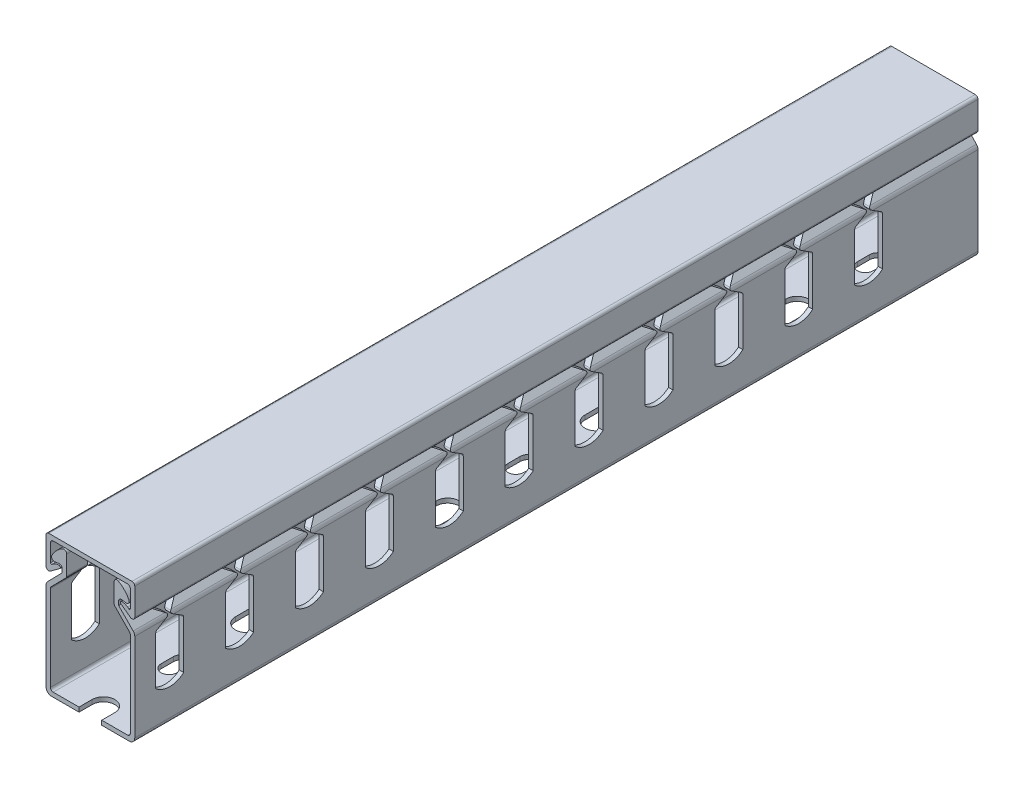
SolidWorks part; units mm, degrees
ref_plane "Front Plane" through (0, 0, 0) normal (0, 0, 1) x (1, 0, 0)
ref_plane "Top Plane" through (0, 0, 0) normal (0, 1, 0) x (1, 0, 0)
ref_plane "Right Plane" through (0, 0, 0) normal (1, 0, 0) x (0, 0, -1)
sketch "Sketch1" plane through (0, 0, 0) normal (0, 0, 1) x (1, 0, 0)
  line L0 (-12.7, 10.6985) -> (12.7, 10.6985) construction
  line L1 (12.7, -20) -> (-12.7, -20) construction
  line L2 (12.7, -20) -> (12.7, 20) construction
  line L3 (12.7, 20) -> (-12.7, 20) construction
  line L4 (-12.7, -20) -> (-12.7, 20) construction
  line L5 (0, 20) -> (0, -20) construction
  line L6 (12.7, 0) -> (-12.7, 0) construction
  line L7 (-12.7, 13.7872) -> (12.7, 13.7872) construction
  line L8 (6.8085, 20) -> (6.8085, 10.6985) construction
  line L9 (-6.8085, 20) -> (6.8085, 10.6985) construction
  line L10 (-6.8085, 20) -> (-6.8085, 10.6985) construction
  line L11 (-12.7, 18.222) -> (12.7, 18.222) construction
  line L12 (-12.7, 13.6284) -> (12.7, 13.6284) construction
  line L13 (-11.4341, 10.8542) -> (-7.685, 13.6284) construction
  line L14 (-10.1877, 13.798) -> (-6.8085, 14.3635) construction
  line L15 (12.7, 7.4) -> (6.8085, 13.4162) construction
  circle A0 centre (-11.9062, 11.4923) radius 0.7938 construction
  circle A1 centre (-10.3187, 14.5809) radius 0.7937 construction
  circle A2 centre (-7.6022, 17.4283) radius 0.7938 construction
  arc A3 (-7.9835, 18.1244) -> (-11.0321, 14.929) centre (-4.4831, 11.7329) ccw construction
  point P0 (0, 0)
  point P4 (11.43, 0)
  point P13 (0, 15.3493)
  point P16 (-11.1125, 13.7872)
  point P21 (-11.1125, 11.4923)
  point P26 (-10.3188, 13.7872)
  point P27 (-10.3188, 13.7872)
  point P28 (-11.1125, 14.5809)
  point P36 (12.7, 7.4)
  dimension "D6" = 7.2873
  dimension "Width" = 25.4
  dimension "Heigth" = 40
  dimension "Wall Thickness" = 1.27
  dimension "Cap Height" = 9.3015
  dimension "Lip Height" = 6.2128
  dimension "D1" = 13.6169
  dimension "D2" = 1.778
  dimension "Lip From Edge" = 1.5875
  dimension "D4" = 0.1588
  dimension "D5" = 36.5
  dimension "D3" = 80.5
  dimension "Shoulder Height" = 27.4
  dimension "D7" = 44.4
sketch "Sketch3" plane through (0, 0, 0) normal (1, 0, 0) x (0, 0, -1)
  line L0 (120.65, 0) -> (-120.65, 0) construction
  line L1 (-120.65, 20) -> (-120.65, -20) construction
  line L2 (-120.65, -20) -> (120.65, -20) construction
  line L3 (120.65, -20) -> (120.65, 20) construction
  line L4 (120.65, 20) -> (-120.65, 20) construction
  line L5 (-106.65, 20) -> (-106.65, 9.8437) construction
  line L6 (-106.65, 9.8437) -> (-110.523, 7.4) construction
  line L7 (-110.523, 7.4) -> (-110.777, 7.4) construction
  line L8 (-110.777, 7.4) -> (-114.65, 9.8437) construction
  line L9 (-114.65, 9.8437) -> (-114.65, 20) construction
  line L10 (-110.777, 7.4) -> (-114.65, 4.9563) construction
  line L11 (-114.65, 4.9563) -> (-114.65, -9.1796) construction
  line L12 (-114.65, -9.1796) -> (-106.65, -9.1796) construction
  line L13 (-106.65, -9.1796) -> (-106.65, 4.9563) construction
  line L14 (-110.523, 7.4) -> (-106.65, 4.9563) construction
  line L15 (-110.65, 7.4) -> (-110.65, -9.1796) construction
  line L16 (-110.65, 7.4) -> (-110.65, 20) construction
  line L17 (-114.65, 4.9563) -> (-106.65, 4.9563) construction
  line L18 (0, 7.4) -> (-110.523, 7.4) construction
  line L19 (-114.65, 9.8437) -> (-114.65, 4.9563) construction
  line L20 (-110.777, 7.4) -> (-114.65, 7.4) construction
  line L21 (-106.65, 4.9563) -> (-94.65, 4.9563) construction
  line L22 (-94.65, 4.9563) -> (-86.65, 4.9563) construction
  line L23 (-90.65, 4.9563) -> (-90.65, -9.1796) construction
  line L24 (6.35, 20) -> (6.35, -20) construction
  line L25 (-6.35, 20) -> (-6.35, -20) construction
  arc A0 (-114.65, -9.1796) -> (-106.65, -9.1796) centre (-110.65, -4.7075) ccw construction
  circle A1 centre (-111.5207, 7.4) radius 0.3969 construction
  circle A2 centre (-109.7793, 7.4) radius 0.3969 construction
  point P29 (-86.65, 4.9563)
  point P30 (-94.65, 4.9563)
  point P31 (-94.65, 4.9563)
  point P32 (-90.65, 4.9563)
  point P34 (6.35, 0)
  point P39 (-6.35, 0)
  dimension "D2" = 6
  dimension "D6" = 0.7937
  dimension "Length" = 241.3
  dimension "Side Cut Out Width" = 8
  dimension "D3" = 6
  dimension "D1" = 10.8204
  dimension "D4" = 64.5
  dimension "D5" = 0.254
  dimension "Cut Spacing" = 12
  dimension "Cut Center To Center" = 20
  dimension "D7" = 127
  dimension "D8" = 127
sketch "Sketch4" plane through (0, 0, 0) normal (0, 1, 0) x (1, 0, 0)
  line L0 (0, -124.4) -> (0, -116.9) construction
  line L1 (-12.7, 120.65) -> (12.7, 120.65) construction
  line L2 (-12.7, 120.65) -> (-12.7, -120.65) construction
  line L3 (-12.7, -120.65) -> (12.7, -120.65) construction
  line L4 (12.7, 120.65) -> (12.7, -120.65) construction
  line L5 (0, -120.65) -> (0, 120.65) construction
  line L6 (-12.7, 0) -> (12.7, 0) construction
  line L7 (-3.25, -124.4) -> (-3.25, -116.9) construction
  line L8 (3.25, -124.4) -> (3.25, -116.9) construction
  line L9 (0, -98.15) -> (0, -94.65) construction
  line L10 (-2.25, -98.15) -> (-2.25, -94.65) construction
  line L11 (2.25, -98.15) -> (2.25, -94.65) construction
  line L12 (0, -75.9) -> (0, -68.4) construction
  line L13 (-3.25, -75.9) -> (-3.25, -68.4) construction
  line L14 (3.25, -75.9) -> (3.25, -68.4) construction
  line L15 (0, -45.4) -> (0, -48.9) construction
  line L16 (2.25, -45.4) -> (2.25, -48.9) construction
  line L17 (-2.25, -45.4) -> (-2.25, -48.9) construction
  line L18 (-12.7, 6.35) -> (12.7, 6.35) construction
  line L19 (-12.7, -6.35) -> (12.7, -6.35) construction
  arc A0 (-3.25, -124.4) -> (3.25, -124.4) centre (0, -124.4) ccw construction
  arc A1 (3.25, -116.9) -> (-3.25, -116.9) centre (0, -116.9) ccw construction
  arc A2 (-2.25, -98.15) -> (2.25, -98.15) centre (0, -98.15) ccw construction
  arc A3 (2.25, -94.65) -> (-2.25, -94.65) centre (0, -94.65) ccw construction
  arc A4 (-3.25, -75.9) -> (3.25, -75.9) centre (0, -75.9) ccw construction
  arc A5 (3.25, -68.4) -> (-3.25, -68.4) centre (0, -68.4) ccw construction
  arc A6 (2.25, -45.4) -> (-2.25, -45.4) centre (0, -45.4) ccw construction
  arc A7 (-2.25, -48.9) -> (2.25, -48.9) centre (0, -48.9) ccw construction
  point P0 (0, 0)
  point P5 (0, -120.65)
  point P13 (0, -96.4)
  point P18 (0, -92.4)
  point P19 (0, -100.4)
  point P20 (0, -113.65)
  point P21 (0, -127.65)
  point P24 (0, -72.15)
  point P31 (0, -47.15)
  point P40 (0, -79.15)
  point P41 (0, -65.15)
  dimension "Large Hole Radius" = 3.25
  dimension "Large Hole Length" = 14
  dimension "Slot With" = 8
  dimension "End Hole Spacing" = 48.5
  dimension "D4" = 24.25
  dimension "Hole Spacing" = 25
  dimension "Mounting Hole Diameter" = 4.5
sketch "Sketch5" plane through (0, 0, 0) normal (0, 0, 1) x (1, 0, 0)
  line L0 (-6.8085, 17.4283) -> (-6.8085, 11.6011)
  line L1 (-6.8085, 20) -> (-6.8085, 10.6985) construction
  line L2 (-6.8085, 11.6011) -> (-11.43, 6.8817)
  line L3 (-11.43, 6.8817) -> (-11.43, -18.73)
  line L4 (-11.43, -18.73) -> (11.43, -18.73)
  line L5 (11.43, -18.73) -> (11.43, 6.8817)
  line L6 (11.43, 6.8817) -> (6.8085, 11.6011)
  line L7 (6.8085, 11.6011) -> (6.8085, 17.4283)
  line L8 (6.8085, 20) -> (6.8085, 10.6985) construction
  line L9 (12.7, 7.4) -> (6.8085, 13.4162) construction
  line L10 (0, 20) -> (0, -20) construction
  line L11 (11.43, 0) -> (12.7, 0) construction
  line L12 (8.0785, 12.1194) -> (6.8085, 12.1194) construction
  line L13 (-10.1877, 13.798) -> (-6.8085, 14.3635) construction
  line L14 (-10.1877, 13.798) -> (-8.0785, 14.151)
  line L15 (-8.0785, 14.151) -> (-8.0785, 12.1194)
  line L16 (-8.0785, 12.1194) -> (-12.7, 7.4)
  line L17 (-12.7, -20) -> (-12.7, 20) construction
  line L18 (-12.7, 7.4) -> (-12.7, -20)
  line L19 (-12.7, -20) -> (12.7, -20)
  line L20 (12.7, -20) -> (12.7, 7.4)
  line L21 (12.7, 7.4) -> (8.0785, 12.1194)
  line L22 (8.0785, 12.1194) -> (8.0785, 14.151)
  line L23 (6.8085, 12.1194) -> (-6.8085, 12.1194) construction
  line L24 (-6.8085, 12.1194) -> (-8.0785, 12.1194) construction
  line L25 (11.43, 6.8817) -> (12.3374, 7.7703) construction
  line L26 (-12.7, 18.222) -> (12.7, 18.222) construction
  line L27 (10.1877, 13.798) -> (8.0785, 14.151)
  line L28 (11.43, -18.73) -> (11.43, -20) construction
  line L29 (-12.7, 20) -> (-12.7, 11.4923)
  line L30 (-12.7, 20) -> (12.7, 20)
  line L31 (-11.4341, 10.8542) -> (-8.7512, 12.8395)
  line L32 (-11.4341, 10.8542) -> (-7.685, 13.6284) construction
  line L33 (12.7, 20) -> (12.7, 11.4923)
  line L34 (12.7, -20) -> (12.7, 20) construction
  line L35 (8.7512, 12.8395) -> (11.4341, 10.8542)
  line L36 (-12.7, 10.6985) -> (12.7, 10.6985) construction
  line L37 (-11.43, 12.4371) -> (-11.43, 18.73)
  line L38 (-11.43, 18.73) -> (11.43, 18.73)
  line L39 (11.43, 18.73) -> (11.43, 12.4371)
  line L40 (-11.43, 18.73) -> (-11.43, 20) construction
  line L41 (-11.43, 18.73) -> (-12.7, 18.73) construction
  line L42 (-11.43, 12.4371) -> (-10.6707, 12.999)
  line L43 (-11.0503, 12.7181) -> (-10.2949, 11.6972) construction
  line L44 (-8.9869, 13.5542) -> (-8.9869, 13.158) construction
  line L45 (10.6707, 12.999) -> (11.43, 12.4371)
  line L46 (10.6707, 12.999) -> (9.9153, 11.9781) construction
  circle A0 centre (-7.6022, 17.4283) radius 0.7938 construction
  arc A1 (-7.9835, 18.1244) -> (-11.0321, 14.929) centre (-4.4831, 11.7329) ccw construction
  arc A2 (-7.9835, 18.1244) -> (-11.0321, 14.929) centre (-4.4831, 11.7329) ccw
  circle A3 centre (-10.3187, 14.5809) radius 0.7937 construction
  arc A4 (-11.0321, 14.929) -> (-10.1877, 13.798) centre (-10.3187, 14.5809) ccw
  arc A5 (-6.8085, 17.4283) -> (-7.9835, 18.1244) centre (-7.6022, 17.4283) ccw
  arc A6 (7.9835, 18.1244) -> (6.8085, 17.4283) centre (7.6022, 17.4282) ccw
  arc A7 (10.1877, 13.798) -> (11.0321, 14.929) centre (10.3187, 14.5809) ccw
  arc A8 (7.9835, 18.1244) -> (11.0321, 14.929) centre (4.4831, 11.7329) cw
  circle A9 centre (-11.9062, 11.4923) radius 0.7938 construction
  arc A10 (-12.7, 11.4923) -> (-11.4341, 10.8542) centre (-11.9062, 11.4923) ccw
  arc A11 (11.4341, 10.8542) -> (12.7, 11.4923) centre (11.9062, 11.4923) ccw
  arc A12 (-8.7512, 12.8395) -> (-8.9869, 13.5542) centre (-8.9869, 13.158) ccw
  arc A13 (-10.6707, 12.999) -> (-8.9869, 13.5542) centre (-8.9869, 10.7234) cw
  arc A14 (8.7512, 12.8395) -> (8.9869, 13.5542) centre (8.9869, 13.158) cw
  arc A15 (8.9869, 13.5542) -> (10.6707, 12.999) centre (8.9869, 10.7234) cw
  point P10 (0, -18.73)
  point P81 (0, 18.73)
  dimension "D2" = 0.3962
  dimension "D1" = 3.3376
extrude "Boss-Extrude1" add sketch "Sketch5" along normal up to vertex (120.65 mm away) and the other way up to vertex (120.65 mm away) up to point (0, -20, 120.65) other way up to point (0, -20, -120.65)
fillet "Fillet1" radius 0.254 2 edges at (-11.43, 12.4371, 0) (11.43, 12.4371, 0)
fillet "Fillet2" radius 0.7937 4 edges at (12.7, 20, 0) (11.43, 18.73, 0) (-11.43, 18.73, 0) (-12.7, 20, 0)
fillet "Fillet3" radius 1.5875 4 edges at (-12.7, -20, 0) (12.7, -20, 0) (12.7, 7.4, 0) (-12.7, 7.4, 0)
fillet "Fillet4" radius 0.7937 8 edges at (-11.43, -18.73, 0) (11.43, -18.73, 0) (8.0785, 14.151, 0) (-8.0785, 14.151, 0) (-11.43, 6.8817, 0) (-6.8085, 11.6011, 0) (6.8085, 11.6011, 0) (11.43, 6.8817, 0)
sketch "Sketch6" plane through (0, 0, 0) normal (1, 0, 0) x (0, 0, -1)
  line L0 (-114.65, 20) -> (-114.65, 10.2814)
  line L1 (-114.65, 4.9563) -> (-114.65, -9.1796) construction
  line L2 (-110.777, 7.4) -> (-114.65, 4.9563) construction
  line L3 (-106.65, -9.1796) -> (-106.65, 4.9563) construction
  line L4 (-110.523, 7.4) -> (-106.65, 4.9563) construction
  line L5 (-106.65, 9.8437) -> (-110.523, 7.4) construction
  line L6 (-106.65, 20) -> (-106.65, 9.8437) construction
  line L7 (-110.777, 7.4) -> (-114.65, 9.8437) construction
  line L8 (-114.65, 4.5186) -> (-114.65, -9.1796)
  line L9 (-111.309, 7.0644) -> (-114.2798, 5.1899)
  line L10 (-106.65, -9.1796) -> (-106.65, 4.5186)
  line L11 (-109.991, 7.0644) -> (-107.0202, 5.1899)
  line L12 (-107.0202, 9.6101) -> (-109.991, 7.7356)
  line L13 (-106.65, 20) -> (-106.65, 10.2814)
  line L14 (-111.309, 7.7356) -> (-114.2798, 9.6101)
  line L15 (-106.65, 20) -> (-114.65, 20)
  circle A0 centre (-109.7793, 7.4) radius 0.3969 construction
  circle A1 centre (-111.5207, 7.4) radius 0.3969 construction
  arc A2 (-109.991, 7.7356) -> (-109.991, 7.0644) centre (-109.7793, 7.4) ccw
  arc A3 (-111.309, 7.0644) -> (-111.309, 7.7356) centre (-111.5207, 7.4) ccw
  arc A4 (-114.65, -9.1796) -> (-106.65, -9.1796) centre (-110.65, -4.7075) ccw construction
  arc A5 (-114.65, -9.1796) -> (-106.65, -9.1796) centre (-110.65, -4.7075) ccw
  arc A6 (-107.0202, 9.6101) -> (-106.65, 10.2814) centre (-107.4437, 10.2814) ccw
  arc A7 (-106.65, 4.5186) -> (-107.0202, 5.1899) centre (-107.4437, 4.5186) ccw
  arc A8 (-114.65, 4.5186) -> (-114.2798, 5.1899) centre (-113.8562, 4.5186) cw
  arc A9 (-114.65, 10.2814) -> (-114.2798, 9.6101) centre (-113.8562, 10.2814) ccw
  dimension "D1" = 0.7937
extrude "Cut-Extrude2" cut sketch "Sketch6" against normal through all both and the other way through all
pattern_linear "LPattern2" count 11 spacing 20 along (0, 0, -1) of "Cut-Extrude2"
sketch "Sketch7" plane through (0, -20, 0) normal (0, -1, 0) x (1, 0, 0)
  line L0 (-3.25, 124.4) -> (-3.25, 116.9) construction
  line L1 (3.25, 124.4) -> (3.25, 116.9) construction
  line L2 (-3.25, 124.4) -> (-3.25, 116.9)
  line L3 (3.25, 124.4) -> (3.25, 116.9)
  line L4 (-2.25, 98.15) -> (-2.25, 94.65) construction
  line L5 (2.25, 98.15) -> (2.25, 94.65) construction
  line L6 (-2.25, 98.15) -> (-2.25, 94.65)
  line L7 (2.25, 98.15) -> (2.25, 94.65)
  arc A0 (3.25, 124.4) -> (-3.25, 124.4) centre (0, 124.4) ccw construction
  arc A1 (-3.25, 116.9) -> (3.25, 116.9) centre (0, 116.9) ccw construction
  arc A2 (3.25, 124.4) -> (-3.25, 124.4) centre (0, 124.4) ccw
  arc A3 (-3.25, 116.9) -> (3.25, 116.9) centre (0, 116.9) ccw
  arc A4 (2.25, 98.15) -> (-2.25, 98.15) centre (0, 98.15) ccw construction
  arc A5 (-2.25, 94.65) -> (2.25, 94.65) centre (0, 94.65) ccw construction
  arc A6 (2.25, 98.15) -> (-2.25, 98.15) centre (0, 98.15) ccw
  arc A7 (-2.25, 94.65) -> (2.25, 94.65) centre (0, 94.65) ccw
extrude "Cut-Extrude3" cut sketch "Sketch7" against normal up to vertex (1.27 mm away) up to point (10.6363, -18.73, 120.65)
sketch "Sketch8" plane through (0, -20, 0) normal (0, -1, 0) x (1, 0, 0)
  line L0 (-2.25, 45.4) -> (-2.25, 48.9) construction
  line L1 (2.25, 45.4) -> (2.25, 48.9) construction
  line L2 (3.25, 75.9) -> (3.25, 68.4) construction
  line L3 (-3.25, 75.9) -> (-3.25, 68.4) construction
  line L4 (-2.25, 45.4) -> (-2.25, 48.9)
  line L5 (2.25, 45.4) -> (2.25, 48.9)
  line L6 (3.25, 75.9) -> (3.25, 68.4)
  line L7 (-3.25, 75.9) -> (-3.25, 68.4)
  arc A0 (-2.25, 45.4) -> (2.25, 45.4) centre (0, 45.4) ccw construction
  arc A1 (2.25, 48.9) -> (-2.25, 48.9) centre (0, 48.9) ccw construction
  arc A2 (3.25, 75.9) -> (-3.25, 75.9) centre (0, 75.9) ccw construction
  arc A3 (-3.25, 68.4) -> (3.25, 68.4) centre (0, 68.4) ccw construction
  arc A4 (-2.25, 45.4) -> (2.25, 45.4) centre (0, 45.4) ccw
  arc A5 (2.25, 48.9) -> (-2.25, 48.9) centre (0, 48.9) ccw
  arc A6 (3.25, 75.9) -> (-3.25, 75.9) centre (0, 75.9) ccw
  arc A7 (-3.25, 68.4) -> (3.25, 68.4) centre (0, 68.4) ccw
extrude "Cut-Extrude4" cut sketch "Sketch8" against normal up to vertex (1.27 mm away) up to point (-3.25, -18.73, 120.65)
pattern_linear "LPattern3" count 6 spacing 50 along (0, 0, -1) of "Cut-Extrude4"
equation "\"D2@Sketch1\"=\"Wall Thickness@Sketch1\"*1.4"
equation "\"D4@Sketch1\"=\"Wall Thickness@Sketch1\"*.125"
equation "\"D2@Sketch3\" = \"Side Cut Out Width@Sketch3\" * .75"
equation "\"D4@Sketch4\" = \"End Hole Spacing@Sketch4\" / 2"
equation "\"D3@LPattern2\"=\"Cut Center To Center@Sketch3\""
equation "\"D1@LPattern2\"=\"Length@Sketch3\"/\"Cut Center To Center@Sketch3\"-1"
equation "\"D1@LPattern3\"=(\"Length@Sketch3\"/50mm)+1"
equation "\"D7@Sketch3\"=\"D8@Sketch3\""
